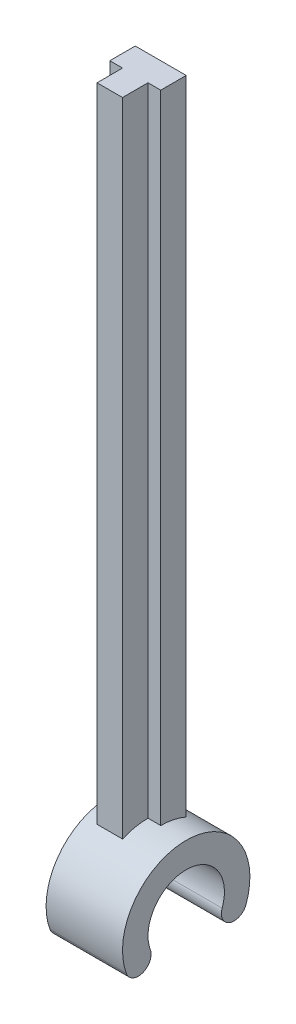
SolidWorks part; units mm, degrees
ref_plane "Front" through (0, 0, 0) normal (0, 0, 1) x (1, 0, 0)
ref_plane "Top" through (0, 0, 0) normal (0, 1, 0) x (1, 0, 0)
ref_plane "Right" through (0, 0, 0) normal (1, 0, 0) x (0, 0, -1)
sketch "Sketch1" plane through (0, 0, 0) normal (1, 0, 0) x (0, 0, -1)
  line L0 (0, 0) -> (-5, 0)
  line L1 (0, 0) -> (-4.6985, -1.7101)
  line L2 (0, 50) -> (0, -50) construction
  line L3 (0, 0) -> (4.6985, -1.7101)
  line L4 (-4.6985, -1.7101) -> (-3.7588, -1.3681)
  circle A0 centre (0, 0) radius 3
  circle A1 centre (0, 0) radius 5
  arc A2 (-4.6985, -1.7101) -> (-2.8191, -1.0261) centre (-3.7588, -1.3681) ccw
  arc A3 (4.6985, -1.7101) -> (2.8191, -1.0261) centre (3.7588, -1.3681) cw
  dimension "D1" = 20
  dimension "D3" = 10
  dimension "D4" = 6
  dimension "D2" = 1
extrude "Boss-Extrude1" add sketch "Sketch1" against normal blind 2 and the other way blind 4 contours L3 A1 L0 A0 | A3 L3 | L0 A1 L1 A0 | L1 A2 region at (0, -0.7055, 4.0009) region at (0, 0.1204, 4) region at (0, -1.7669, 3.6136) region at (0, -1.7669, -3.6136)
sketch "Sketch2" plane through (0, 0, 0) normal (1, 0, 0) x (0, 0, -1)
  line L0 (0, 0) -> (0, 5)
  line L1 (0, 5) -> (0, 3)
  line L2 (0, 3) -> (-2, 3)
  line L3 (0, 55) -> (0, 3)
  line L4 (-2, 3) -> (2, 3)
  line L5 (-2, 3) -> (-2, 55)
  line L6 (-2, 55) -> (2, 55)
  line L7 (2, 3) -> (2, 55)
  arc A0 (4.6985, -1.7101) -> (-4.6985, -1.7101) centre (0, 0) ccw construction
  dimension "D1" = 2
  dimension "D2" = 2
  dimension "D3" = 4
  dimension "D4" = 52
extrude "Boss-Extrude2" add sketch "Sketch2" along normal blind 2 and the other way blind 2 contours L4 L7 L6 L3 L0 region at (0, 29, -1)
sketch "Sketch3" plane through (0, 0, 0) normal (1, 0, 0) x (0, 0, -1)
  line L9 (0, 3) -> (-2, 3)
  line L10 (0, 3) -> (0, 55)
  line L11 (0, 55) -> (-2, 55)
  line L12 (-2, 3) -> (-2, 55)
  arc A0 (2.8191, -1.0261) -> (-2.8191, -1.0261) centre (0, 0) ccw construction
  dimension "D1" = 52
  dimension "D2" = 2
extrude "Boss-Extrude3" add sketch "Sketch3" along normal blind 1 and the other way blind 1
